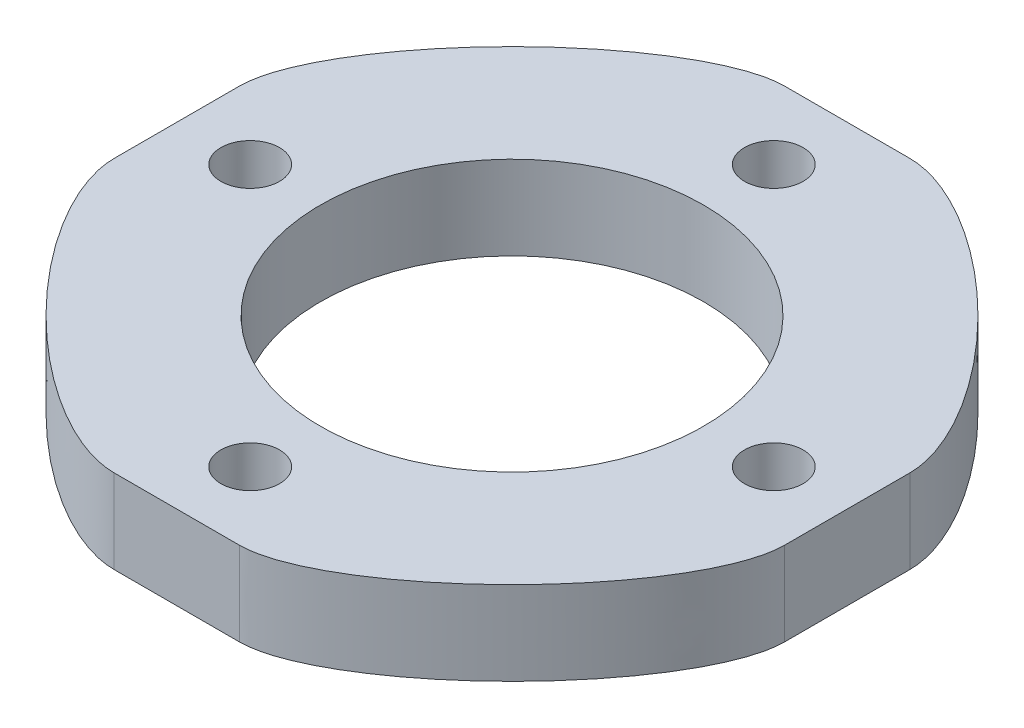
SolidWorks part; units mm, degrees
ref_plane "Front" through (0, 0, 0) normal (0, 0, 1) x (1, 0, 0)
ref_plane "Top" through (0, 0, 0) normal (0, 1, 0) x (1, 0, 0)
ref_plane "Right" through (0, 0, 0) normal (1, 0, 0) x (0, 0, -1)
sketch "Sketch1" plane through (0, 0, 0) normal (0, 1, 0) x (1, 0, 0)
  line L1 (0, 0) -> (32, 0)
  line L2 (0, 0) -> (0, -32)
  line L3 (0, -32) -> (32, -32)
  line L4 (32, 0) -> (32, -32)
  dimension "D1" = 32
  dimension "D2" = 32
extrude "Boss-Extrude1" add sketch "Sketch1" along normal blind 4
sketch "Sketch2" plane through (0, 0, 0) normal (0, -1, 0) x (-1, 0, 0)
  line L0 (-32, 0) -> (0, 0) construction
  line L1 (-32, -32) -> (-32, 0) construction
  line L2 (0, -32) -> (-32, -32) construction
  line L3 (0, 0) -> (0, -32) construction
  circle A0 centre (-16, -16) radius 9.15
  circle A1 centre (-16, -28.5) radius 1.4
  circle A2 centre (-28.5, -16) radius 1.4
  circle A3 centre (-16, -3.5) radius 1.4
  circle A4 centre (-3.5, -16) radius 1.4
  dimension "D1" = 18.3
  dimension "D2" = 2.8
  dimension "D3" = 2.8
  dimension "D4" = 2.8
  dimension "D5" = 2.8
  dimension "D6" = 3.5
  dimension "D7" = 3.5
  dimension "D8" = 3.5
  dimension "D9" = 3.5
extrude "Cut-Extrude1" cut sketch "Sketch2" against normal blind 4
fillet "Fillet1" radius 13 4 edges at (0, 2, 0) (32, 2, 0) (32, 2, 32) (0, 2, 32) conic rho 0.25
equation "\"滑动-垂直孔\" = 0.6"
equation "\"滑动-水平孔\"= 0.3"
equation "\"松动-垂直孔\" = 0.3"
equation "\"松动-水平孔\"= 0.1"
equation "\"正常-垂直孔\" = 0.15"
equation "\"正常-水平孔\"= 0"
equation "\"紧缩-垂直孔\"= 0"
equation "\"紧缩-水平孔\"= - 0.1"
equation "\"D1@Sketch2\"=\"松动-垂直孔\"+18mm"
equation "\"D2@Sketch2\"=\"松动-垂直孔\"+2.5"
equation "\"D3@Sketch2\"=\"松动-垂直孔\"+2.5"
equation "\"D4@Sketch2\"=\"松动-垂直孔\"+2.5"
equation "\"D5@Sketch2\"=\"松动-垂直孔\"+2.5"
